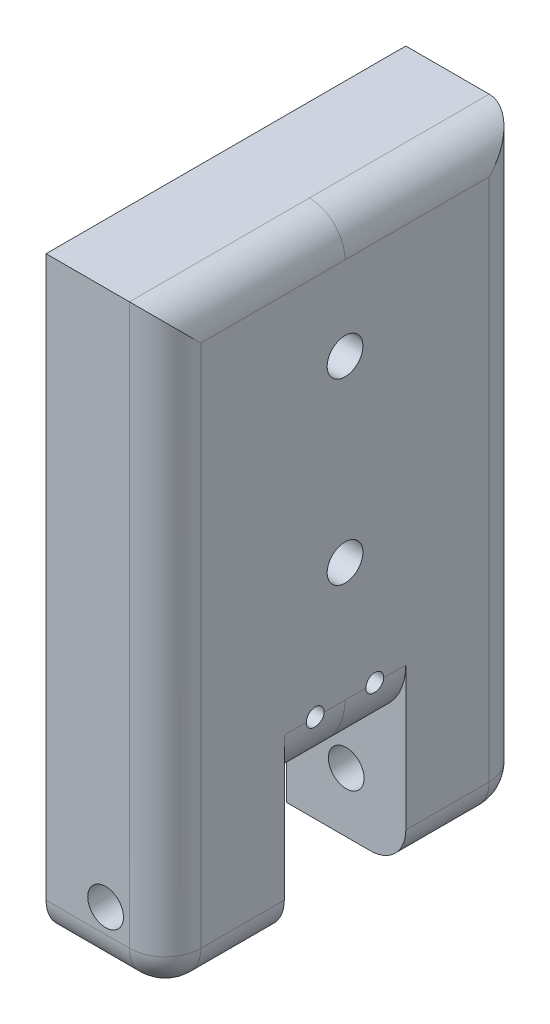
SolidWorks part; units mm, degrees
ref_plane "Front Plane" through (0, 0, 0) normal (0, 0, 1) x (1, 0, 0)
ref_plane "Top Plane" through (0, 0, 0) normal (0, 1, 0) x (1, 0, 0)
ref_plane "Right Plane" through (0, 0, 0) normal (1, 0, 0) x (0, 0, -1)
sketch "Sketch1" plane through (0, 0, 0) normal (1, 0, 0) x (0, 0, -1)
  line L0 (5.15, 0) -> (15.15, 0)
  line L1 (15.15, 0) -> (15.15, 50)
  line L2 (15.15, 50) -> (0.05, 50)
  line L3 (0.05, 50) -> (0.05, 41.5)
  line L4 (5.15, 0) -> (5.15, 10)
  line L5 (5.15, 10) -> (0.05, 10)
  line L8 (0.05, 38.5) -> (0.05, 26.5)
  line L10 (0.05, 23.5) -> (0.05, 10)
  arc A0 (0.05, 38.5) -> (0.05, 41.5) centre (0.05, 40) ccw
  arc A1 (0.05, 23.5) -> (0.05, 26.5) centre (0.05, 25) ccw
  circle A3 centre (2.55, 15) radius 0.75
  dimension "D6" = 3
  dimension "D7" = 3
  dimension "D8" = 1.5
  dimension "D1" = 50
  dimension "D2" = 10
  dimension "D3" = 5.15
  dimension "D4" = 10
  dimension "D5" = 5.1
  dimension "D9" = 10
  dimension "D10" = 15
  dimension "D11" = 2.5
  dimension "D12" = 5
extrude "Boss-Extrude1" add sketch "Sketch1" along normal blind 10
fillet "Fillet1" radius 3 4 edges at (10, 25, -15.15) (10, 50, -7.6) (10, 0, -10.15) (5, 0, -15.15)
fillet "Fillet2" radius 5 2 edges at (0, 10, -2.6) (10, 10, -2.6)
sketch "Sketch2" plane through (0, 0, -15.15) normal (0, 0, -1) x (-1, 0, 0)
  line L0 (-10, 5) -> (0, 5) construction
  line L1 (-10, 3) -> (-10, 47) construction
  line L2 (0, 3) -> (0, 50) construction
  line L3 (-5, 5) -> (-5, 0) construction
  line L4 (0, 0) -> (-7, 0) construction
  circle A0 centre (-5, 5) radius 1.5
  point P0 (-5, 6.3723)
  point P12 (0, 0)
  dimension "D2" = 3
  dimension "D1" = 5
extrude "Cut-Extrude1" cut sketch "Sketch2" against normal up to surface (10 mm away) up to face at (5.4369, 6.7179, -5.15)
mirror "Mirror10" about plane through (10, 50, -0.05) normal (0, 0, -1) of "Cut-Extrude1", "Boss-Extrude1", "Fillet1", "Fillet2"
